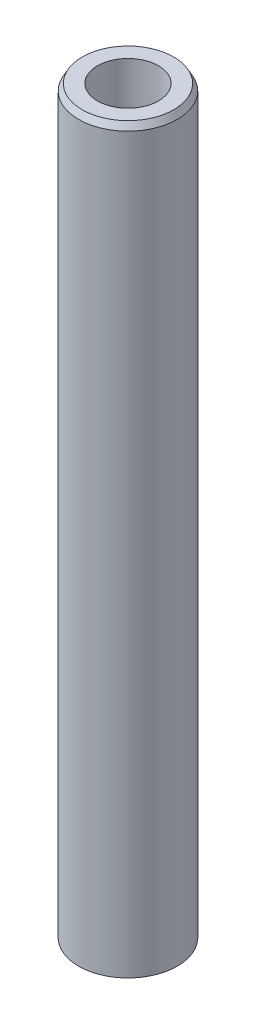
SolidWorks part; units mm, degrees
ref_plane "Front Plane" through (0, 0, 0) normal (0, 0, 1) x (1, 0, 0)
ref_plane "Top Plane" through (0, 0, 0) normal (0, 1, 0) x (1, 0, 0)
ref_plane "Right Plane" through (0, 0, 0) normal (1, 0, 0) x (0, 0, -1)
sketch "Sketch1" plane through (0, 0, 0) normal (0, 1, 0) x (1, 0, 0)
  circle A0 centre (0, 0) radius 27.5
  dimension "SHAFT_OD" = 55
extrude "Boss-Extrude1" add sketch "Sketch1" along normal blind 414.266
sketch "Sketch2" plane through (0, 0, 0) normal (0, 1, 0) x (1, 0, 0)
  circle A0 centre (0, 0) radius 16.9997
  dimension "BORE_D" = 33.9993
extrude "Cut-Extrude1" cut sketch "Sketch2" along normal through all
chamfer "Chamfer1" distance 3.6508 angle 28.871 2 edges at (0, 414.266, 27.5) (0, 0, 27.5) first distance on face at (0, 414.266, 27.5) first distance on face at (0, 0, 16.9997)
